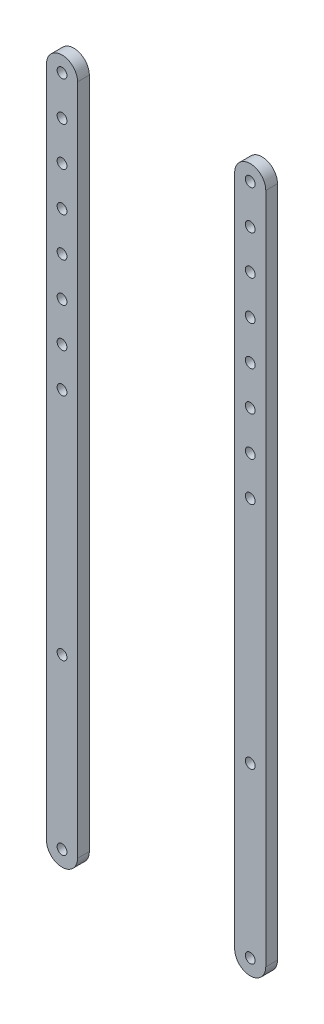
SolidWorks part; units mm, degrees
other "Markup1"
sketch "Sketch2" plane through (0.0463, -24.9703, 0) normal (0.1644, -0.1295, 0.9779) x (0.9753, 0.1699, -0.1414)
ref_plane "Front Plane" through (0, 0, 0) normal (0, 0, 1) x (1, 0, 0)
ref_plane "Top Plane" through (0, 0, 0) normal (0, 1, 0) x (1, 0, 0)
ref_plane "Right Plane" through (0, 0, 0) normal (1, 0, 0) x (0, 0, -1)
sketch "Skeleton" plane through (0, 0, 0) normal (0, 0, 1) x (1, 0, 0)
  line L12 (-10.421, 7.5043) -> (-18.2135, 7.5043)
  line L13 (0.0463, -8.9838) -> (0.0463, 9.017)
  line L14 (-129.9283, 9.017) -> (-129.9283, -8.983)
  line L15 (-111.6685, 7.5043) -> (-119.461, 7.5043)
  line L16 (-107.6558, 19.017) -> (-107.6558, 11.517)
  line L17 (-28.2135, 25.0043) -> (-101.6685, 25.0043)
  line L18 (-22.2262, 11.517) -> (-22.2262, 19.017)
  line L19 (-18.2135, -7.4703) -> (-10.421, -7.4703)
  line L20 (-22.2262, -18.983) -> (-22.2262, -11.483)
  line L21 (-101.6685, -24.9703) -> (-28.2135, -24.9703)
  line L22 (-107.6558, -11.483) -> (-107.6558, -18.983)
  line L23 (-119.461, -7.4703) -> (-111.6685, -7.4703)
  line L24 (-64.941, -24.9703) -> (-64.941, 25.0043) construction
  line L25 (-129.9283, 0.017) -> (0, 0) construction
  arc A24 (-22.2262, 11.517) -> (-18.2135, 7.5043) centre (-18.2135, 11.517) ccw
  arc A25 (-10.421, 7.5043) -> (-8.4147, 9.356) centre (-10.421, 9.517) ccw
  arc A26 (0.0463, 9.017) -> (-8.4147, 9.356) centre (-4.191, 9.0164) ccw
  arc A27 (-8.4147, -9.322) -> (0.0463, -8.9838) centre (-4.191, -8.9828) ccw
  arc A28 (-8.4147, -9.322) -> (-10.421, -7.4703) centre (-10.421, -9.483) ccw
  arc A29 (-119.461, -7.4703) -> (-121.4673, -9.322) centre (-119.461, -9.483) ccw
  arc A30 (-129.9283, -8.983) -> (-121.4673, -9.322) centre (-125.691, -8.9824) ccw
  arc A31 (-121.4673, 9.356) -> (-129.9283, 9.017) centre (-125.691, 9.0165) ccw
  arc A32 (-121.4673, 9.356) -> (-119.461, 7.5043) centre (-119.461, 9.517) ccw
  arc A33 (-111.6685, 7.5043) -> (-107.6558, 11.517) centre (-111.6685, 11.517) ccw
  arc A34 (-101.6685, 25.0043) -> (-107.6558, 19.017) centre (-101.6685, 19.017) ccw
  arc A35 (-22.2262, 19.017) -> (-28.2135, 25.0043) centre (-28.2135, 19.017) ccw
  arc A36 (-18.2135, -7.4703) -> (-22.2262, -11.483) centre (-18.2135, -11.483) ccw
  arc A37 (-28.2135, -24.9703) -> (-22.2262, -18.983) centre (-28.2135, -18.983) ccw
  arc A38 (-107.6558, -18.983) -> (-101.6685, -24.9703) centre (-101.6685, -18.983) ccw
  arc A39 (-107.6558, -11.483) -> (-111.6685, -7.4703) centre (-111.6685, -11.483) ccw
  arc A40 (-90.1911, -21.4831) -> (-87.6911, -21.4831) centre (-88.9411, -21.4831) ccw
  arc A41 (-87.6911, -21.4831) -> (-90.1911, -21.4831) centre (-88.9411, -21.4831) ccw
  arc A42 (-42.1911, -21.4831) -> (-39.6911, -21.4831) centre (-40.9411, -21.4831) ccw
  arc A43 (-39.6911, -21.4831) -> (-42.1911, -21.4831) centre (-40.9411, -21.4831) ccw
  arc A44 (-42.1911, 21.5169) -> (-39.6911, 21.5169) centre (-40.9411, 21.5169) ccw
  arc A45 (-39.6911, 21.5169) -> (-42.1911, 21.5169) centre (-40.9411, 21.5169) ccw
  arc A46 (-87.6911, 21.5169) -> (-90.1911, 21.5169) centre (-88.9411, 21.5169) ccw
  arc A47 (-90.1911, 21.5169) -> (-87.6911, 21.5169) centre (-88.9411, 21.5169) ccw
sketch "Sketch3" plane through (0, 0, 0) normal (0, 0, 1) x (1, 0, 0)
  line L0 (-88.9411, -21.4831) -> (-88.9411, 150.0117) construction
  line L1 (-92.9072, -21.4831) -> (-92.9072, 150.0117)
  line L2 (-84.9749, -21.4831) -> (-84.9749, 150.0117)
  line L3 (-64.941, -24.9703) -> (-64.941, 118.5169) construction
  line L4 (-40.9409, -21.4831) -> (-40.9409, 150.0117) construction
  line L5 (-36.9748, -21.4831) -> (-36.9748, 150.0117)
  line L6 (-44.9071, -21.4831) -> (-44.9071, 150.0117)
  line L7 (-129.9283, 0.017) -> (0, 0) construction
  line L8 (-129.9283, 0.017) -> (0, 0) construction
  arc A0 (-92.9072, -21.4831) -> (-84.9749, -21.4831) centre (-88.9411, -21.4831) ccw
  arc A1 (-84.9749, 150.0117) -> (-92.9072, 150.0117) centre (-88.9411, 150.0117) ccw
  arc A2 (-36.9748, -21.4831) -> (-44.9071, -21.4831) centre (-40.9409, -21.4831) cw
  arc A3 (-44.9071, 150.0117) -> (-36.9748, 150.0117) centre (-40.9409, 150.0117) cw
  arc A4 (-87.6911, -21.4831) -> (-90.1911, -21.4831) centre (-88.9411, -21.4831) ccw construction
  arc A5 (-90.1911, -21.4831) -> (-87.6911, -21.4831) centre (-88.9411, -21.4831) ccw construction
  arc A6 (-39.6911, -21.4831) -> (-42.1911, -21.4831) centre (-40.9411, -21.4831) ccw construction
  arc A7 (-42.1911, -21.4831) -> (-39.6911, -21.4831) centre (-40.9411, -21.4831) ccw construction
  arc A8 (-39.6911, 21.5169) -> (-42.1911, 21.5169) centre (-40.9411, 21.5169) ccw construction
  arc A9 (-42.1911, 21.5169) -> (-39.6911, 21.5169) centre (-40.9411, 21.5169) ccw construction
  arc A10 (-87.6911, 21.5169) -> (-90.1911, 21.5169) centre (-88.9411, 21.5169) ccw construction
  arc A11 (-90.1911, 21.5169) -> (-87.6911, 21.5169) centre (-88.9411, 21.5169) ccw construction
  arc A12 (-87.6911, -21.4831) -> (-90.1911, -21.4831) centre (-88.9411, -21.4831) ccw
  arc A13 (-90.1911, -21.4831) -> (-87.6911, -21.4831) centre (-88.9411, -21.4831) ccw
  arc A14 (-39.6911, -21.4831) -> (-42.1911, -21.4831) centre (-40.9411, -21.4831) ccw
  arc A15 (-42.1911, -21.4831) -> (-39.6911, -21.4831) centre (-40.9411, -21.4831) ccw
  arc A16 (-39.6911, 21.5169) -> (-42.1911, 21.5169) centre (-40.9411, 21.5169) ccw
  arc A17 (-42.1911, 21.5169) -> (-39.6911, 21.5169) centre (-40.9411, 21.5169) ccw
  arc A18 (-87.6911, 21.5169) -> (-90.1911, 21.5169) centre (-88.9411, 21.5169) ccw
  arc A19 (-90.1911, 21.5169) -> (-87.6911, 21.5169) centre (-88.9411, 21.5169) ccw
  arc A22 (-87.6911, 150.0117) -> (-90.1911, 150.0117) centre (-88.9411, 150.0117) ccw
  arc A23 (-90.1911, 150.0117) -> (-87.6911, 150.0117) centre (-88.9411, 150.0117) ccw
  arc A24 (-39.6909, 150.0117) -> (-42.191, 150.0117) centre (-40.9409, 150.0117) ccw
  arc A25 (-42.191, 150.0117) -> (-39.6909, 150.0117) centre (-40.9409, 150.0117) ccw
  circle A26 centre (-88.9411, 140.0117) radius 1.25
  circle A27 centre (-88.9411, 130.0117) radius 1.25
  circle A28 centre (-88.9411, 120.0117) radius 1.25
  circle A29 centre (-40.9409, 140.0117) radius 1.25
  circle A30 centre (-40.9409, 130.0117) radius 1.25
  circle A31 centre (-40.9409, 120.0117) radius 1.25
  circle A32 centre (-88.9411, 110.0117) radius 1.25
  circle A33 centre (-40.9409, 110.0117) radius 1.25
  circle A34 centre (-88.9411, 100.0117) radius 1.25
  circle A35 centre (-40.9409, 100.0117) radius 1.25
  circle A36 centre (-88.9411, 90.0117) radius 1.25
  circle A37 centre (-40.9409, 90.0117) radius 1.25
  circle A38 centre (-88.9411, 80.0117) radius 1.25
  circle A39 centre (-40.9409, 80.0117) radius 1.25
  point P3 (-88.9411, 64.2643)
  point P8 (-64.941, 25.0043)
  point P9 (-64.941, -24.9703)
  point P16 (-40.9409, 64.2643)
  dimension "D2" = 140
  dimension "D1" = 150
  dimension "D3" = 130
  dimension "D4" = 120
  dimension "D5" = 5
extrude "Boss-Extrude1" add sketch "Sketch3" along normal blind 3
fillet "Fillet1" radius 0.5 2 edges at (-39.6911, -21.4831, 0) (-39.6911, 21.5169, 0)
fillet "Fillet2" radius 0.5 2 edges at (-87.6911, -21.4831, 0) (-87.6911, 21.5169, 0)
